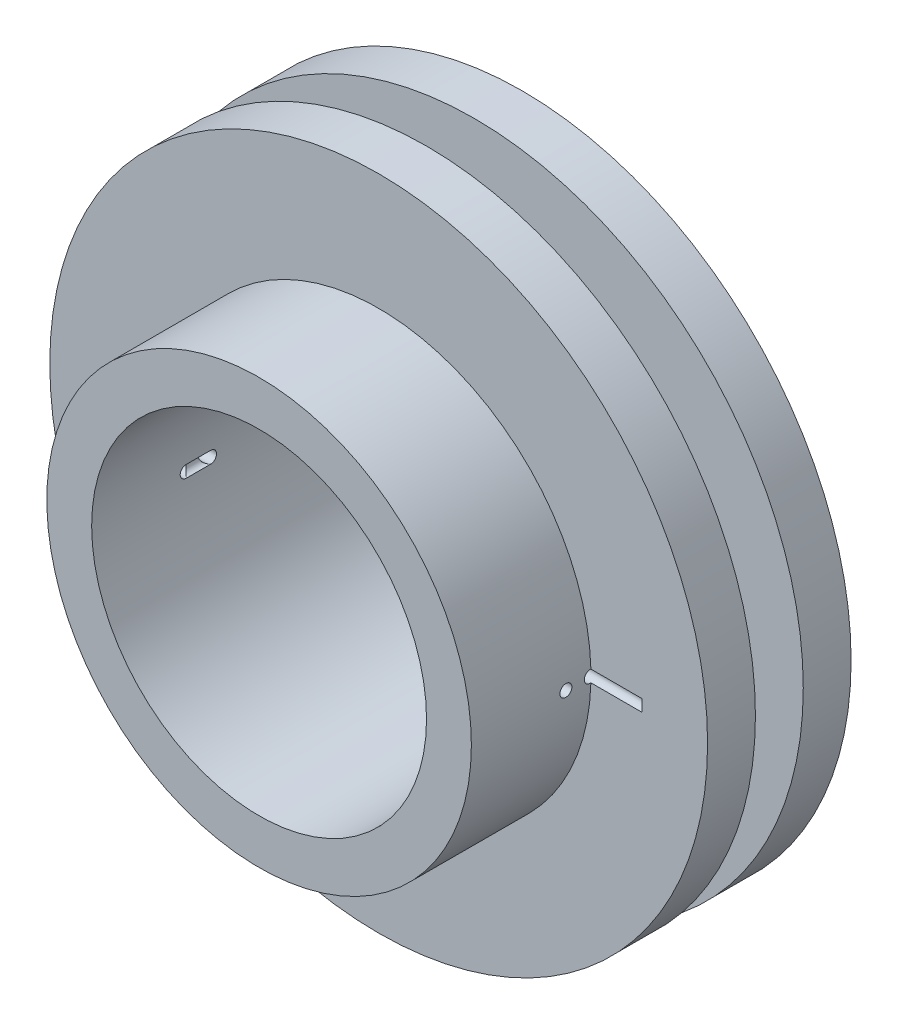
SolidWorks part; units mm, degrees
material "ABS"
ref_plane "Front Plane" through (0, 0, 0) normal (0, 0, 1) x (1, 0, 0)
ref_plane "Top Plane" through (0, 0, 0) normal (0, 1, 0) x (1, 0, 0)
ref_plane "Right Plane" through (0, 0, 0) normal (1, 0, 0) x (0, 0, -1)
sketch "Sketch1" plane through (0, 0, 0) normal (0, 0, 1) x (1, 0, 0)
  circle A0 centre (0, 0) radius 13.75
  dimension "D1" = 27.5
extrude "Boss-Extrude1" add sketch "Sketch1" along normal blind 2
sketch "Sketch2" plane through (0, 0, 0) normal (0, 0, 1) x (1, 0, 0)
  circle A0 centre (0, 0) radius 8.5
  dimension "D1" = 17
extrude "Boss-Extrude2" add sketch "Sketch2" along normal blind 6
sketch "Sketch3" plane through (0, 0, 0) normal (0, 0, 1) x (1, 0, 0)
  circle A0 centre (0, 0) radius 13.75
  dimension "D1" = 27.5
extrude "Boss-Extrude3" add sketch "Sketch3" along normal blind 2 from offset 4
sketch "Sketch5" plane through (0, 0, 0) normal (0, 0, 1) x (1, 0, 0)
  circle A0 centre (0, 0) radius 7
extrude "Cut-Extrude2" cut sketch "Sketch5" along normal through all
sketch "Sketch6" plane through (0, 0, 0) normal (0, 0, 1) x (1, 0, 0)
  circle A0 centre (0, 0) radius 7
  circle A1 centre (0, 0) radius 8.875
  dimension "D1" = 17.75
extrude "Boss-Extrude4" add sketch "Sketch6" along normal blind 5 from surface starting at face at (13.75, 0, 6)
sketch "Sketch16" plane through (0, 0, 0) normal (0, 0, 1) x (1, 0, 0)
  circle A0 centre (-7, 0) radius 0.25
  circle A1 centre (0, 0) radius 7 construction
  circle A2 centre (7, 0) radius 0.25
sketch "Sketch17" plane through (0, 0, 0) normal (1, 0, 0) x (0, 0, -1)
  circle A0 centre (-6.0297, 0) radius 0.25
  circle A1 centre (-7.0484, 0) radius 0.25
extrude "Cut-Extrude7" cut sketch "Sketch17" against normal blind 11 and the other way blind 11
extrude "Cut-Extrude13" cut sketch "Sketch16" along normal blind 1 from offset 6
ref_plane "Plane2" through (-11, 0.2482, 6) normal (0, 1, 0) x (1, 0, 0)
